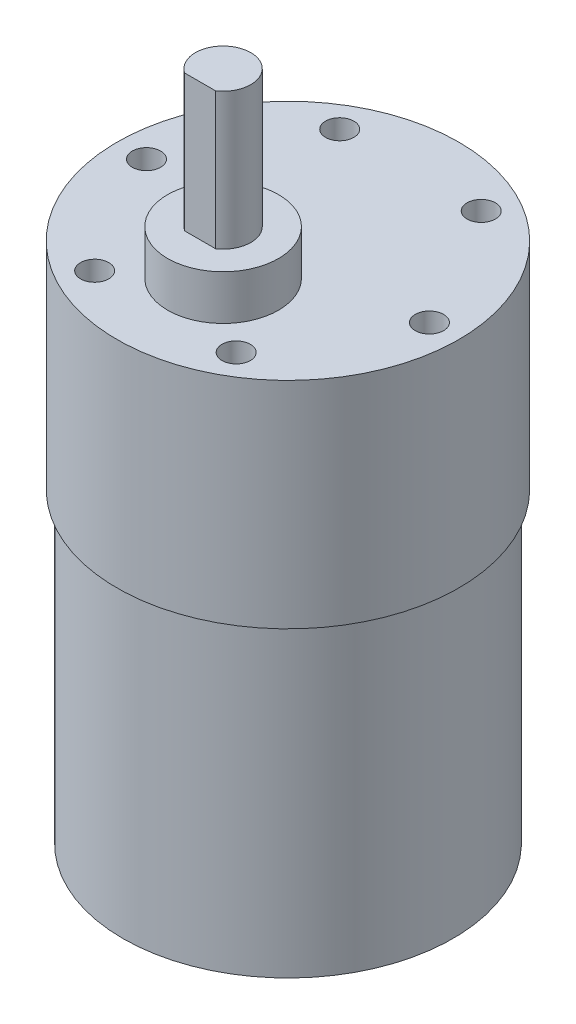
SolidWorks part; units mm, degrees
ref_plane "Front Plane" through (0, 0, 0) normal (0, 0, 1) x (1, 0, 0)
ref_plane "Top Plane" through (0, 0, 0) normal (0, 1, 0) x (1, 0, 0)
ref_plane "Right Plane" through (0, 0, 0) normal (1, 0, 0) x (0, 0, -1)
sketch "Sketch1" plane through (0, 0, 0) normal (0, 1, 0) x (1, 0, 0)
  circle A0 centre (0, 0) radius 17.78
  dimension "D1" = 35.56
extrude "Boss-Extrude1" add sketch "Sketch1" along normal blind 33.02
sketch "Sketch2" plane through (0, 33.02, 0) normal (0, 1, 0) x (1, 0, 0)
  circle A0 centre (0, 0) radius 18.415
  dimension "D1" = 36.83
extrude "Boss-Extrude2" add sketch "Sketch2" along normal blind 23.1775
sketch "Sketch3" plane through (0, 56.1975, 0) normal (0, 1, 0) x (1, 0, 0)
  line L0 (0, 0) -> (23.3389, 0) construction
  line L1 (0, 0) -> (0, 22.8201) construction
  circle A0 centre (15.24, 0) radius 1.524
  circle A1 centre (7.62, -13.1982) radius 1.524
  circle A2 centre (-7.62, -13.1982) radius 1.524
  circle A3 centre (-15.24, 0) radius 1.524
  circle A4 centre (-7.62, 13.1982) radius 1.524
  circle A5 centre (7.62, 13.1982) radius 1.524
  point P19 (0, 0)
  dimension "D2" = 3.048
  dimension "D1" = 15.24
  dimension "D3" = 6
extrude "Cut-Extrude1" cut sketch "Sketch3" against normal blind 12.7
sketch "Sketch4" plane through (0, 56.1975, 0) normal (0, 1, 0) x (1, 0, 0)
  line L0 (0, 0) -> (18.415, 0) construction
  line L1 (0, 0) -> (0, -18.415) construction
  circle A0 centre (0, 0) radius 18.415 construction
  circle A1 centre (0, -6.985) radius 5.969
  dimension "D1" = 11.938
  dimension "D2" = 11.43
extrude "Boss-Extrude3" add sketch "Sketch4" along normal blind 4.826
sketch "Sketch5" plane through (0, 61.0235, 0) normal (0, 1, 0) x (1, 0, 0)
  line L0 (0, -6.985) -> (0, -9.9695) construction
  line L1 (0, -6.985) -> (2.9845, -6.985) construction
  line L2 (0, -9.4615) -> (1.6656, -9.4615) construction
  line L3 (1.6656, -9.4615) -> (-1.6656, -9.4615)
  circle A0 centre (0, -6.985) radius 2.9845 construction
  arc A1 (1.6656, -9.4615) -> (-1.6656, -9.4615) centre (0, -6.985) ccw
  dimension "D1" = 5.969
  dimension "D2" = 0.508
extrude "Boss-Extrude4" add sketch "Sketch5" along normal blind 14.732 contours L3 A1 region at (0, 61.0235, 6.8702)
